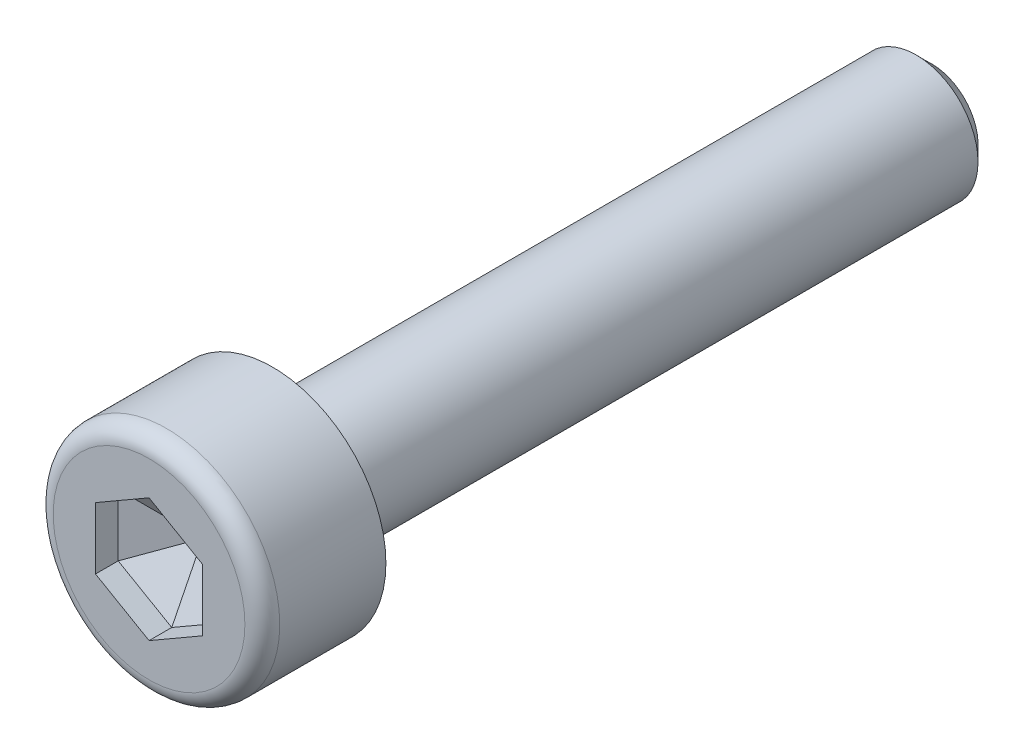
SolidWorks part; units mm, degrees
ref_plane "前视基准面" through (0, 0, 0) normal (0, 0, 1) x (1, 0, 0)
ref_plane "上视基准面" through (0, 0, 0) normal (0, 1, 0) x (1, 0, 0)
ref_plane "右视基准面" through (0, 0, 0) normal (1, 0, 0) x (0, 0, -1)
sketch "草图1" plane through (0, 0, 0) normal (0, 0, 1) x (1, 0, 0)
  circle A0 centre (0, 0) radius 2.75
  dimension "dk" = 5.5
extrude "凸台-拉伸1" add sketch "草图1" along normal blind 3
ref_axis "基准轴1" through (0, 0, 3) along (0, 0, -1)
sketch "草图2" plane through (0, 0, 3) normal (0, 0, 1) x (1, 0, 0)
  line L1 (1.3, 0.7506) -> (0, 1.5011)
  line L2 (0, 1.5011) -> (-1.3, 0.7506)
  line L3 (-1.3, 0.7506) -> (-1.3, -0.7506)
  line L4 (-1.3, -0.7506) -> (0, -1.5011)
  line L5 (0, -1.5011) -> (1.3, -0.7506)
  line L6 (1.3, -0.7506) -> (1.3, 0.7506)
  circle A0 centre (0, 0) radius 1.3 construction
  dimension "s" = 2.6
extrude "切除-拉伸1" cut sketch "草图2" against normal blind 1.3
sketch "草图3" plane through (0, 0, 0) normal (0, 0, -1) x (-1, 0, 0)
  circle A0 centre (0, 0) radius 1.5
  dimension "d" = 3
extrude "凸台-拉伸2" add sketch "草图3" along normal blind 16
cosmetic thread "装饰螺纹线1" parameters "b"=4.9, "D2"=1.221
chamfer "倒角1" distance 0.375 angle 45 1 edges at (-1.5, 0, -16)
fillet "圆角1" radius 0.4231 1 edges at (2.75, 0, 3)
chamfer "倒角2" distance 0.7493 angle 60 6 edges at (-1.3, 0, 1.7) (-0.65, 1.1258, 1.7) (0.65, 1.1258, 1.7) (1.3, 0, 1.7) (-0.65, -1.1258, 1.7) (0.65, -1.1258, 1.7) first distance on face at (-1.3, 0, 2.35) first distance on face at (-0.65, 1.1258, 2.35) first distance on face at (0.65, 1.1258, 2.35) first distance on face at (1.3, 0, 2.35) first distance on face at (-0.65, -1.1258, 2.35) first distance on face at (0.65, -1.1258, 2.35)
fillet "圆角2" radius 0.1 1 edges at (1.5, 0, 0)
ref_plane "基准面1" through (0, 0, 0) normal (0, 0, -1) x (-1, 0, 0)
equation "\"D1@倒角2\" = \"s@草图2\" / 3.47"
equation "\"D1@圆角1\"= \"dk@草图1\" / 13"
equation "\"D1@倒角1\"= \"d@草图3\" / 8"
equation "\"D1@圆角2\"= \"d@草图3\" / \"d@草图3\" * 0.1"
